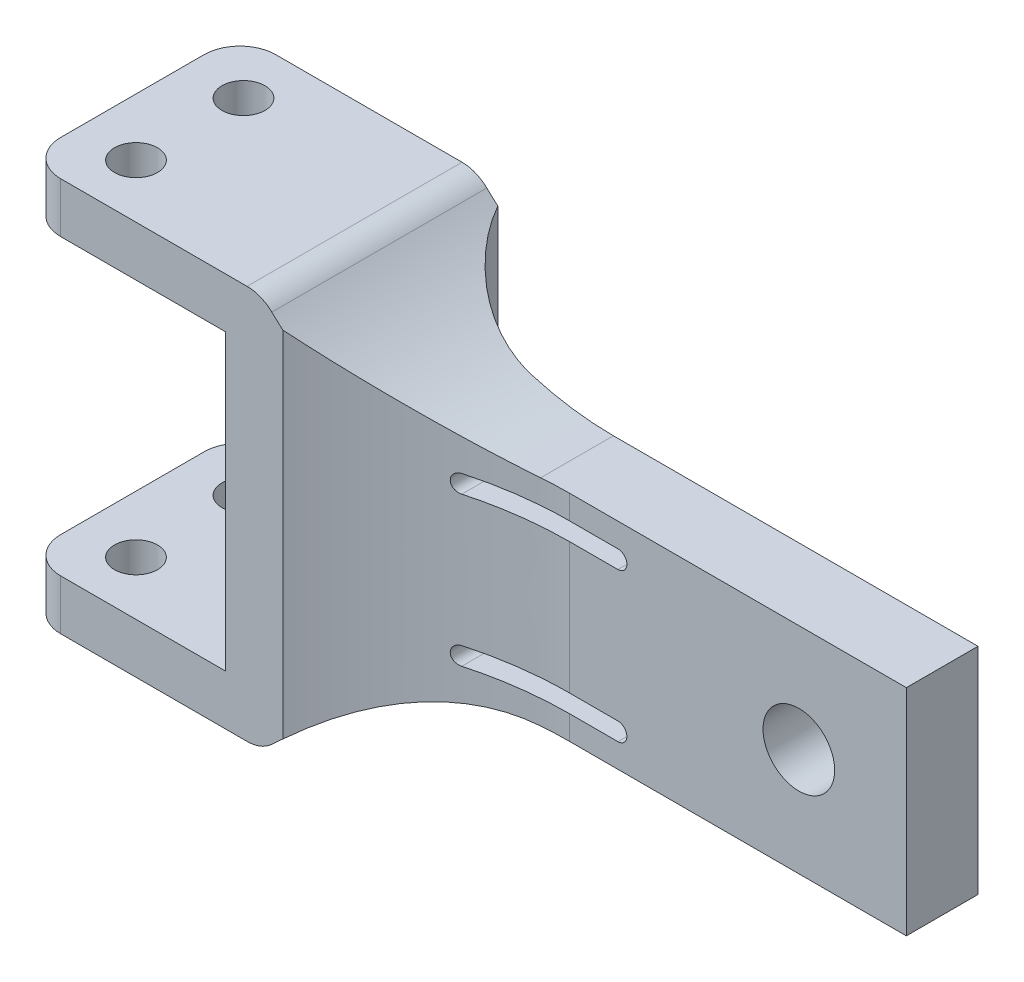
SolidWorks part; units mm, degrees
ref_plane "前视基准面" through (0, 0, 0) normal (0, 0, 1) x (1, 0, 0)
ref_plane "上视基准面" through (0, 0, 0) normal (0, 1, 0) x (1, 0, 0)
ref_plane "右视基准面" through (0, 0, 0) normal (1, 0, 0) x (0, 0, -1)
other "Configuration Table"
sketch "草图1" plane through (0, 0, 0) normal (0, 0, 1) x (1, 0, 0)
  line L1 (0, 0) -> (85, 0)
  line L2 (0, 0) -> (0, 30)
  line L3 (0, 30) -> (85, 30)
  line L4 (85, 0) -> (85, 30)
  dimension "D1" = 30
  dimension "D2" = 85
extrude "凸台-拉伸1" add sketch "草图1" along normal blind 10
sketch "草图2" plane through (0, 0, 0) normal (0, 0, -1) x (-1, 0, 0)
  line L0 (-85, 15) -> (0, 15) construction
  line L1 (-85, 0) -> (-85, 30) construction
  line L2 (0, 30) -> (0, 0) construction
  line L3 (-44.75, 30) -> (-44.75, 0) construction
  line L4 (-85, 30) -> (0, 30) construction
  line L5 (0, 0) -> (-85, 0) construction
  line L6 (-44.75, 25.4) -> (-24.75, 25.4) construction
  line L7 (-44.75, 26.65) -> (-24.75, 26.65)
  line L8 (-44.75, 24.15) -> (-24.75, 24.15)
  line L9 (-44.75, 4.6) -> (-24.75, 4.6) construction
  line L10 (-44.75, 5.85) -> (-24.75, 5.85)
  line L11 (-44.75, 3.35) -> (-24.75, 3.35)
  circle A0 centre (-70, 15) radius 5
  arc A2 (-44.75, 26.65) -> (-44.75, 24.15) centre (-44.75, 25.4) ccw
  arc A3 (-24.75, 24.15) -> (-24.75, 26.65) centre (-24.75, 25.4) ccw
  arc A4 (-44.75, 5.85) -> (-44.75, 3.35) centre (-44.75, 4.6) ccw
  arc A5 (-24.75, 3.35) -> (-24.75, 5.85) centre (-24.75, 4.6) ccw
  point P16 (-34.75, 25.4)
  point P23 (-34.75, 4.6)
  point P28 (0, 0)
  dimension "D1" = 10
  dimension "D2" = 70
  dimension "D3" = 25.25
  dimension "D4" = 2.5
  dimension "D5" = 2.5
  dimension "D6" = 20.8
  dimension "D7" = 4.6
  dimension "D8" = 20
extrude "切除-拉伸1" cut sketch "草图2" against normal up to next
sketch "草图3" plane through (0, 0, 10) normal (0, 0, 1) x (1, 0, 0)
  line L5 (0, 0) -> (85, 0) construction
  line L6 (0, 30) -> (8, 30)
  line L7 (0, 30) -> (0, 0)
  line L8 (0, 0) -> (8, 0)
  line L9 (8, 30) -> (8, 0)
  dimension "D1" = 8
extrude "凸台-拉伸2" add sketch "草图3" along normal blind 10 and the other way blind 20 separate body
sketch "草图5" plane through (0, 30, 0) normal (0, 1, 0) x (1, 0, 0)
  line L1 (0, 10) -> (8, 10)
  line L2 (0, 10) -> (0, -20)
  line L3 (0, -20) -> (8, -20)
  line L4 (8, 10) -> (8, -20)
extrude "凸台-拉伸3" add sketch "草图5" along normal blind 12.5
sketch "草图6" plane through (0, 0, 0) normal (-1, 0, 0) x (0, 0, 1)
  line L0 (20, 42.5) -> (20, 0) construction
  line L1 (-10, 42.5) -> (20, 42.5)
  line L2 (-10, 42.5) -> (-10, 35.5)
  line L3 (-10, 35.5) -> (20, 35.5)
  line L4 (20, 42.5) -> (20, 35.5)
  dimension "D1" = 7
extrude "凸台-拉伸4" add sketch "草图6" along normal blind 28
sketch "草图7" plane through (0, 42.5, 0) normal (0, 1, 0) x (1, 0, 0)
  line L0 (-28, -5) -> (-9.7126, -5) construction
  line L1 (-28, -20) -> (-28, 10) construction
  line L2 (8, -20) -> (8, 10) construction
  line L3 (-28, -20) -> (8, -20) construction
  circle A0 centre (-20, 2.5) radius 3
  circle A1 centre (-20, -12.5) radius 3
  dimension "D2" = 6
  dimension "D3" = 6
  dimension "D1" = 28
  dimension "D4" = 15
  dimension "D5" = 7.5
extrude "切除-拉伸2" cut sketch "草图7" against normal up to next
fillet "圆角1" radius 5 3 edges at (-28, 39, -10) (-28, 39, 20) (8, 42.5, 5)
ref_plane "基准面1" through (0, 15, 0) normal (0, 1, 0) x (1, 0, 0)
mirror "镜向1" about plane through (0, 15, 0) normal (0, 1, 0) of "凸台-拉伸4", "切除-拉伸2", "圆角1", "凸台-拉伸3"
fillet "圆角2" radius 50 1 edges at (8, 15, 10) first distance on face at (8, 15, 5)
fillet "圆角3" radius 16 1 edges at (8, 15, 0) first distance on face at (46.5, 15, 0)
fillet "圆角4" radius 40 2 edges
